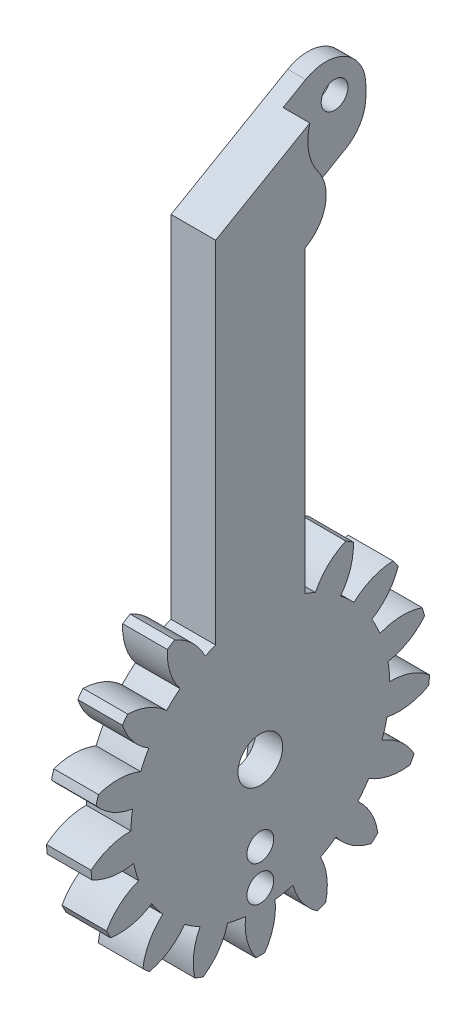
SolidWorks part; units mm, degrees
ref_plane "Plane1" through (0, 0, 0) normal (0, 0, 1) x (1, 0, 0)
ref_plane "Plane2" through (0, 0, 0) normal (0, 1, 0) x (1, 0, 0)
ref_plane "Plane3" through (0, 0, 0) normal (1, 0, 0) x (0, 0, -1)
sketch "HoldingSke" plane through (0, 0, 0) normal (0, 1, 0) x (1, 0, 0)
  line L0 (0, 0) -> (0.4782, -0.1462)
  line L1 (-15, 0) -> (100, 0) construction
  line L2 (0, 0) -> (-2.1039, 2.3779)
  line L3 (0, 0) -> (-11.863, 4.5341)
  line L4 (0, 0) -> (8.2586, 2.5249)
  line L5 (0, 0) -> (-46.8476, -17.4728)
  line L6 (0, 0) -> (-8.2896, -5.593)
  line L7 (-2.1039, 2.3779) -> (8.659, 51.2077)
  line L8 (-76.2, 54.61) -> (-75.3, 54.61)
  line L9 (-71.009, 38.7566) -> (-53.1078, 45.2721)
  line L10 (-76.2, 71.12) -> (104.1128, 71.12)
  line L11 (0, 0) -> (-10, 0)
  line L12 (-76.2, 101.6) -> (-76.133, 101.6)
  line L13 (24.9733, 27.94) -> (52.9518, 28.4284)
  line L14 (24.9733, 27.94) -> (24.9743, 27.94)
  line L15 (24.9733, 27.94) -> (100.4006, 29.5858)
  line L16 (-63.627, -2) -> (-12.827, -2)
  circle A0 centre (0, 0) radius 2.5
  circle A1 centre (0, 0) radius 14.499
  circle A2 centre (0, 0) radius 37.5
  circle A3 centre (0, 0) radius 2.5
  dimension "Num_teeth" = 17
  dimension "Pitch_radius" = 180.3128
  dimension "Width" = 10
  dimension "Thickness" = 10
sketch "BasProSke" plane through (0, 0, 0) normal (0, 1, 0) x (1, 0, 0)
  line L0 (-10, 0) -> (60, 0) construction
  line L1 (0, 0) -> (0, 19)
  line L2 (0, 0) -> (10, 0)
  line L3 (10, 0) -> (10, 19)
  line L4 (10, 19) -> (0, 19)
  dimension "Thickness" = 10
  dimension "Diameter" = 38
revolve "Base-Revolve" add sketch "BasProSke" angle 360 about L0
sketch "TooCutSke" plane through (0, 0, 0) normal (1, 0, 0) x (0, 0, -1)
  line L1 (0, 0) -> (0, 107) construction
  line L2 (0, 0) -> (-1.6857, 16.9162) construction
  line L3 (0, 0) -> (-6.2247, 33.2991) construction
  line L4 (-1.6857, 16.9162) -> (-3.1123, 16.6495) construction
  arc A0 (1.0204, 14.4631) -> (-1.0204, 14.4631) centre (0, 0) ccw
  arc A1 (3.0261, 18.7832) -> (-3.0261, 18.7832) centre (0, 0) ccw
  circle A2 centre (0, 0) radius 17 construction
  circle A3 centre (0, 0) radius 15.9748 construction
  arc A4 (-1.0204, 14.4631) -> (-3.0261, 18.7832) centre (-7.8003, 13.9409) ccw
  arc A5 (3.0261, 18.7832) -> (1.0204, 14.4631) centre (7.8003, 13.9409) ccw
extrude "ToothCut" cut sketch "TooCutSke" along normal through all
fillet "Breaks" [suppressed] radius 0.04 tangent propagation no
fillet "RootFillets" [suppressed] radius 0.501
pattern_circular "TeethCuts" count 17 every 21.176 about axis through (-10, 0, 0) along (1, 0, 0) of "ToothCut", "RootFillets", "Breaks"
sketch "HubNeaOneSke" plane through (0, 0, 0) normal (-1, 0, 0) x (0, 0, 1)
  circle A0 centre (0, 0) radius 14.499
  dimension "Diameter" = 28.998
extrude "HubNearOne" [suppressed] add sketch "HubNeaOneSke" along normal blind 40.0019
sketch "HubNeaBotSke" plane through (0, 0, 0) normal (-1, 0, 0) x (0, 0, 1)
  circle A0 centre (0, 0) radius 14.499
  dimension "Diameter" = 28.998
extrude "HubNearBoth" [suppressed] add sketch "HubNeaBotSke" along normal blind 20.001
ref_plane "FarPln" through (10, 0, 0) normal (1, 0, 0) x (0, 0, -1)
sketch "HubFarSke" plane through (10, 0, 0) normal (1, 0, 0) x (0, 0, -1)
  circle A0 centre (0, 0) radius 14.499
  dimension "Diameter" = 28.998
extrude "HubFar" [suppressed] add sketch "HubFarSke" along normal blind 20.001
sketch "BorSke" plane through (0, 0, 0) normal (1, 0, 0) x (0, 0, -1)
  circle A0 centre (0, 0) radius 2.5
  dimension "Diameter" = 5
extrude "Bore" cut sketch "BorSke" along normal mid plane 100.0039
sketch "KeySke" plane through (0, 0, 0) normal (1, 0, 0) x (0, 0, -1)
  line L0 (-1, 0) -> (-1, 3.4)
  line L1 (-1, 3.4) -> (1, 3.4)
  line L2 (1, 3.4) -> (1, 0)
  line L3 (0, 0) -> (0, 34) construction
  line L4 (-1, 0) -> (1, 0)
  dimension "Width" = 2
extrude "Keyway" [suppressed] cut sketch "KeySke" along normal mid plane 100.0039
pattern_circular "Keyway2" [suppressed] count 2 every 90 about axis through (-10, 0, 0) along (1, 0, 0)
sketch "Sketch1" plane through (0, 0, 0) normal (0, 0, 1) x (1, 0, 0)
  line L1 (-5, 20) -> (5, 20)
  line L2 (-5, 20) -> (-5, -20)
  line L3 (-5, -20) -> (5, -20)
  line L4 (5, 20) -> (5, -20)
  line L5 (-5, 20) -> (5, -20) construction
  line L6 (-5, -20) -> (5, 20) construction
  point P0 (0, 0)
  dimension "D1" = 10
  dimension "D2" = 40
extrude "Cut-Extrude1" cut sketch "Sketch1" against normal blind 20 and the other way blind 20
sketch "Sketch2" plane through (5, 0, 0) normal (-1, 0, 0) x (0, 0, 1)
  line L0 (0, 0) -> (0, -21.0725) construction
  line L1 (-3.961, -0.5571) -> (-2, -14.5)
  line L2 (4, 0) -> (2, -14.5)
  circle A0 centre (0, 0) radius 4
  circle A1 centre (0, -14.5) radius 2
  dimension "D1" = 8
  dimension "D2" = 4
  dimension "D3" = 14.5
sketch "Sketch4" plane through (10, 0, 0) normal (1, 0, 0) x (0, 0, -1)
  line L0 (0, 0) -> (0, 50) construction
  line L1 (0, 50) -> (17.3205, 60) construction
  line L2 (5, 0) -> (5, 47.1132)
  line L3 (5, 47.1132) -> (14.8205, 52.7831)
  line L4 (-5, 0) -> (-5, 52.8868)
  line L5 (-5, 52.8868) -> (14.8205, 64.3301)
  line L6 (14.8205, 64.3301) -> (14.8205, 52.7831)
  line L7 (-5, 0) -> (-2.5, 0)
  line L8 (5, 47.1132) -> (19.8205, 55.6699) construction
  line L9 (2.5, 0) -> (5, 0)
  circle A0 centre (0, 0) radius 2.5 construction
  arc A1 (2.5, 0) -> (-2.5, 0) centre (0, 0) ccw
  dimension "D1" = 120
  dimension "D2" = 50
  dimension "D3" = 20
  dimension "D4" = 5
  dimension "D5" = 5
extrude "Boss-Extrude1" add sketch "Sketch4" against normal blind 5
sketch "Sketch5" plane through (5, 0, 0) normal (-1, 0, 0) x (0, 0, 1)
  circle A0 centre (-11.3205, 57.3301) radius 1.5
  dimension "D1" = 3
  dimension "D2" = 7
  dimension "D3" = 3.5
extrude "Cut-Extrude5" cut sketch "Sketch5" against normal through all
fillet "Fillet2" radius 4.5 2 edges at (7.5, 52.7831, -14.8205) (7.5, 64.3301, -14.8205)
sketch "Sketch7" plane through (10, 0, 0) normal (1, 0, 0) x (0, 0, -1)
  line L0 (11.3205, 57.3301) -> (20.7223, 62.7583) construction
  line L1 (8.0705, 60.433) -> (-5, 52.8868) construction
  line L2 (14.3205, 52.134) -> (23.7223, 57.5621)
  line L3 (8.3205, 62.5263) -> (17.7223, 67.9544)
  line L4 (17.7223, 67.9544) -> (23.7223, 57.5621)
  circle A0 centre (11.3205, 57.3301) radius 6
  dimension "D1" = 12
  dimension "D2" = 6
  dimension "D3" = 6
extrude "Cut-Extrude7" cut sketch "Sketch7" against normal blind 3 contours L0 A0 L2 L4 | A0 L0 L4 L3 | A0 region at (10, 64.0486, -16.2616) region at (10, 58.25, -19.6095) region at (10, 58.8391, -16.9521)
extrude "Cut-Extrude8" cut sketch "Sketch2" against normal blind 2 contours L0 A0 L1 A1 | A1 L0 | L0 A1 | A0 L0 A1 L2 | L2 A0 region at (5, -7.769, 1.5735) region at (5, -7.7482, -1.5886) region at (5, 0.0003, -0.0021) region at (5, -14.5, 0.8488) region at (5, -14.5, -0.8488)
sketch "Sketch8" plane through (7, 0, 0) normal (-1, 0, 0) x (0, 0, 1)
  circle A0 centre (0, -8.45) radius 1.5
  circle A1 centre (0, -12.45) radius 1.5
  circle A2 centre (0, 0) radius 2.5 construction
  dimension "D1" = 3
  dimension "D2" = 3
  dimension "D3" = 8.45
  dimension "D4" = 12.45
extrude "Cut-Extrude9" cut sketch "Sketch8" against normal through all
fillet "Fillet3" radius 4.5 1 edges at (8.5, 51.4493, -12.5102)
equation "' \"Module@HoldingSke\" = 6.35"
equation "' \"Num_teeth@HoldingSke\" = 12"
equation "' \"Ap@HoldingSke\" =  20"
equation "' \"Ap@HoldingSke\" = 20"
equation "'\"Width@HoldingSke\" = 0.2.5 * 25.4"
equation "' \"Hub_dia@HoldingSke\"= 1 * 25.4"
equation "' \"Hub_dia@HoldingSke\" = 1 * 25.4"
equation "' \"Overall_len@HoldingSke\" = 1.0 * 25.4"
equation "' \"Bore@HoldingSke\" = 0.75 * 25.4"
equation "' \"T_dim@HoldingSke\" = 0.1 * 25.4"
equation "' \"Width@KeySke\" = 0.25 * 25.4"
equation "' \"Show_teeth@HoldingSke\" = 13"
equation "' \"Backlash@HoldingSke\" = 0.009 * 25.4"
equation "' \"Addendum_fac@HoldingSke\" = 1.0"
equation "' \"Dedendum_fac@HoldingSke\" = 1.25"
equation "' \"Dedendum_add@HoldingSke\" = 0.00005 * 25.4"
equation "' \"Clearance_fac@HoldingSke\" = 0.25"
equation "\"Pitch@HoldingSke\" = 1 / \"Module@HoldingSke\""
equation "\"Overcut_dia@TooCutSke\" = (\"Num_teeth@HoldingSke\" + 2 * \"Addendum_fac@HoldingSke\") / \"Pitch@HoldingSke\" + 0.002 * 25.4"
equation "\"Pitch_dia@TooCutSke\" = \"Num_teeth@HoldingSke\" / \"Pitch@HoldingSke\""
equation "\"Base_dia@TooCutSke\" = \"Num_teeth@HoldingSke\" / \"Pitch@HoldingSke\" * cos((\"Ap@HoldingSke\"  * 3.14159265 / 180))"
equation "\"Root_dia@TooCutSke\" = (\"Num_teeth@HoldingSke\" + 2) / \"Pitch@HoldingSke\" - 2 * (\"Addendum_fac@HoldingSke\" + \"Dedendum_fac@HoldingSke\") / \"Pitch@HoldingSke\" - \"Dedendum_add@HoldingSke\" * 2"
equation "\"Half_ang@TooCutSke\" = 180 / \"Num_teeth@HoldingSke\""
equation "\"Half_CT@TooCutSke\" = \"Num_teeth@HoldingSke\" / \"Pitch@HoldingSke\" * sin((3.14159265 / 2 / \"Num_teeth@HoldingSke\")) / 2 - 7 * \"Backlash@HoldingSke\" / 4"
equation "\"Flank_rad@TooCutSke\" = \"Num_teeth@HoldingSke\" / \"Pitch@HoldingSke\" / 5"
equation "\"Radius@RootFillets\" = \"Clearance_fac@HoldingSke\" / \"Pitch@HoldingSke\" + \"Dedendum_add@HoldingSke\""
equation "\"Break_rad@Breaks\" = 0.02 / \"Pitch@HoldingSke\""
equation "\"Thickness@HoldingSke\" = \"Width@HoldingSke\""
equation "\"OAL@HoldingSke\" = \"Thickness@HoldingSke\""
equation "\"MHD@HoldingSke\" = (\"Num_teeth@HoldingSke\" + 2) / \"Pitch@HoldingSke\" - 2 * (\"Addendum_fac@HoldingSke\" + \"Dedendum_fac@HoldingSke\")  / \"Pitch@HoldingSke\" - \"Dedendum_add@HoldingSke\" * 2"
equation "\"MBD@HoldingSke\" = (\"Num_teeth@HoldingSke\" + 2) / \"Pitch@HoldingSke\" - 2 * (\"Addendum_fac@HoldingSke\" + \"Dedendum_fac@HoldingSke\")  / \"Pitch@HoldingSke\" - \"Dedendum_add@HoldingSke\" * 2 - 0.002 * 25.4"
equation "\"MHD@HoldingSke\" = ((sgn( \"MHD@HoldingSke\" - \"Hub_dia@HoldingSke\" )-1)*( \"MHD@HoldingSke\" - \"Hub_dia@HoldingSke\" ))/-2+ \"Hub_dia@HoldingSke\""
equation "\"MBD@HoldingSke\" = ((sgn( \"MBD@HoldingSke\" - \"Bore@HoldingSke\" )-1)*( \"MBD@HoldingSke\" - \"Bore@HoldingSke\" ))/-2+ \"Bore@HoldingSke\""
equation "\"OAL@HoldingSke\" = ((sgn( \"OAL@HoldingSke\" - \"Overall_len@HoldingSke\" )+1)*( \"OAL@HoldingSke\" - \"Overall_len@HoldingSke\" ))/2 + \"Overall_len@HoldingSke\" + 0.000002 * 25.4"
equation "\"Num_teeth@TeethCuts\" = int( \"Show_teeth@HoldingSke\" ) + 1"
equation "\"Num_teeth@TeethCuts\" = ((sgn( \"Num_teeth@TeethCuts\" - \"Num_teeth@HoldingSke\" )-1)*( \"Num_teeth@TeethCuts\" - \"Num_teeth@HoldingSke\" ))/-2+ \"Num_teeth@HoldingSke\""
equation "\"Num_teeth@TeethCuts\" = ((sgn( \"Num_teeth@TeethCuts\" - 2.0)+1)*( \"Num_teeth@TeethCuts\" - 2.0))/2 +2.0"
equation "\"Angle@TeethCuts\" = 360.0 / \"Num_teeth@HoldingSke\""
equation "\"Diameter@BasProSke\" = (\"Num_teeth@HoldingSke\" + 2 * \"Addendum_fac@HoldingSke\") / \"Pitch@HoldingSke\""
equation "\"Thickness@BasProSke\"  = \"Thickness@HoldingSke\""
equation "' \"Fillet_rad@BasProSke\" =  \"Thickness@HoldingSke\" * 0.05"
equation "' \"Fillet_rad@BasProSke\" = \"Thickness@HoldingSke\" * 0.05"
equation "\"MHD@HoldingSke\" = ((sgn( \"MHD@HoldingSke\" - \"Root_dia@TooCutSke\" )-1)*( \"MHD@HoldingSke\" - \"Root_dia@TooCutSke\" ))/-2+ \"Root_dia@TooCutSke\""
equation "\"Diameter@HubNeaOneSke\" = \"MHD@HoldingSke\""
equation "\"Length@HubNearOne\" = \"OAL@HoldingSke\" - \"Thickness@BasProSke\""
equation "\"Diameter@HubNeaBotSke\" = \"MHD@HoldingSke\""
equation "\"Length@HubNearBoth\" = ( \"OAL@HoldingSke\" - \"Thickness@BasProSke\" ) / 2.0"
equation "\"Thickness@FarPln\" = \"Thickness@BasProSke\""
equation "\"Diameter@HubFarSke\" = \"MHD@HoldingSke\""
equation "\"Length@HubFar\" = ( \"OAL@HoldingSke\" - \"Thickness@BasProSke\" ) / 2.0"
equation "\"Diameter@BorSke\" = \"MBD@HoldingSke\""
equation "\"D1@Bore\" = \"OAL@HoldingSke\" * 2.0"
equation "\"D1@Keyway\" = \"OAL@HoldingSke\" * 2.0"
equation "\"Offset@KeySke\" = \"T_dim@HoldingSke\" + \"MBD@HoldingSke\" / 2.0"
